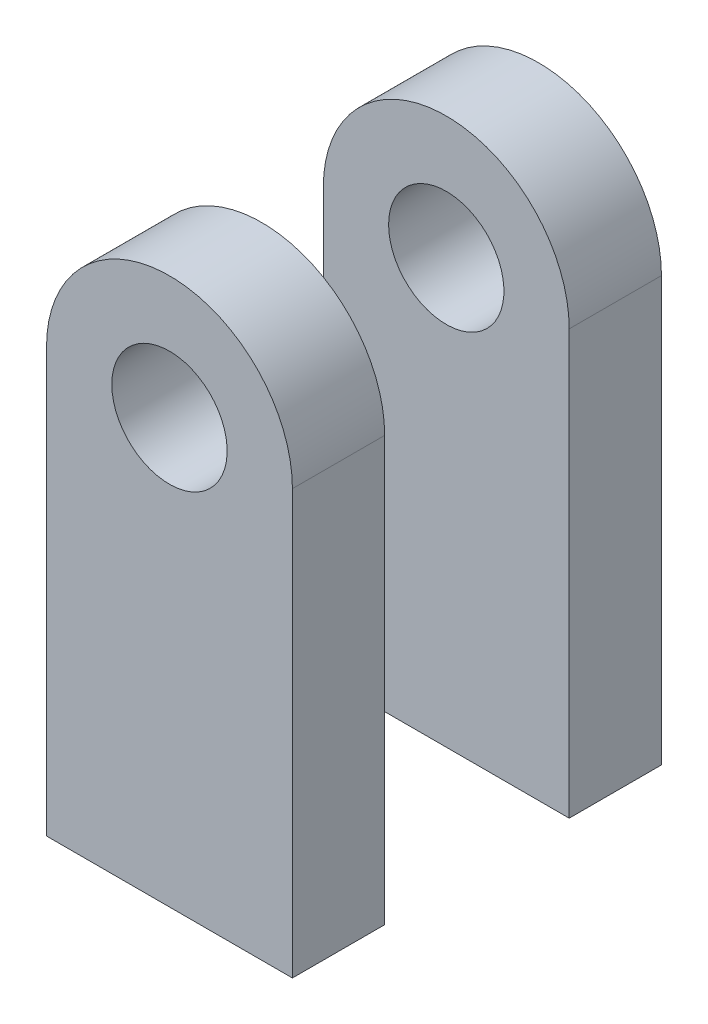
SolidWorks part; units mm, degrees
ref_plane "Front Plane" through (0, 0, 0) normal (0, 0, 1) x (1, 0, 0)
ref_plane "Top Plane" through (0, 0, 0) normal (0, 1, 0) x (1, 0, 0)
ref_plane "Right Plane" through (0, 0, 0) normal (1, 0, 0) x (0, 0, -1)
sketch "Sketch1" plane through (0, 0, 0) normal (0, 0, 1) x (1, 0, 0)
  line L1 (0, 0) -> (10.1533, 0)
  line L2 (0, 0) -> (0, 6.35)
  line L4 (10.1533, 0) -> (10.1533, 6.35)
  arc A0 (0, 6.35) -> (10.1533, 6.35) centre (5.0767, 6.35) cw
  circle A1 centre (5.0767, 6.35) radius 2.3813
  dimension "D1" = 4.7625
  dimension "D3" = 5.0767
  dimension "D2" = 6.35
extrude "Boss-Extrude1" add sketch "Sketch1" along normal mid plane 15.24 contours A0 L2 L1 L4 A1 region at (0.1529, 3.175, 0)
sketch "Sketch2" plane through (0, 0, 0) normal (-1, 0, 0) x (0, 0, 1)
  line L0 (-7.62, 0) -> (-7.62, 6.35) construction
  line L1 (-3.81, 0) -> (3.81, 0)
  line L2 (-3.81, 0) -> (-3.81, 24.1712)
  line L3 (-3.81, 24.1712) -> (3.81, 24.1712)
  line L4 (3.81, 0) -> (3.81, 24.1712)
  line L5 (7.62, 0) -> (7.62, 6.35) construction
  line L6 (7.62, 0) -> (-7.62, 0) construction
  dimension "D1" = 3.81
  dimension "D2" = 3.81
  dimension "D3" = 0
  dimension "D4" = 24.1712
extrude "Cut-Extrude1" cut sketch "Sketch2" against normal blind 25.4 contours L2 L1 L4 L3
ref_plane "Plane1" through (5.0767, 0, 0) normal (-1, 0, 0) x (0, 0, 1)
sketch "Sketch3" plane through (0, 0, 0) normal (0, -1, 0) x (1, 0, 0)
  line L1 (0, 7.62) -> (10.1533, 7.62)
  line L2 (0, 7.62) -> (0, 3.81)
  line L3 (0, 3.81) -> (10.1533, 3.81)
  line L4 (10.1533, 7.62) -> (10.1533, 3.81)
  line L10 (0, -3.81) -> (10.1533, -3.81)
  line L11 (0, -3.81) -> (0, -7.62)
  line L12 (0, -7.62) -> (10.1533, -7.62)
  line L13 (10.1533, -3.81) -> (10.1533, -7.62)
extrude "Boss-Extrude2" add sketch "Sketch3" along normal blind 11.15
ref_axis "Axis1" through (5.0767, 6.35, -3.81) along (0, 0, -1)
